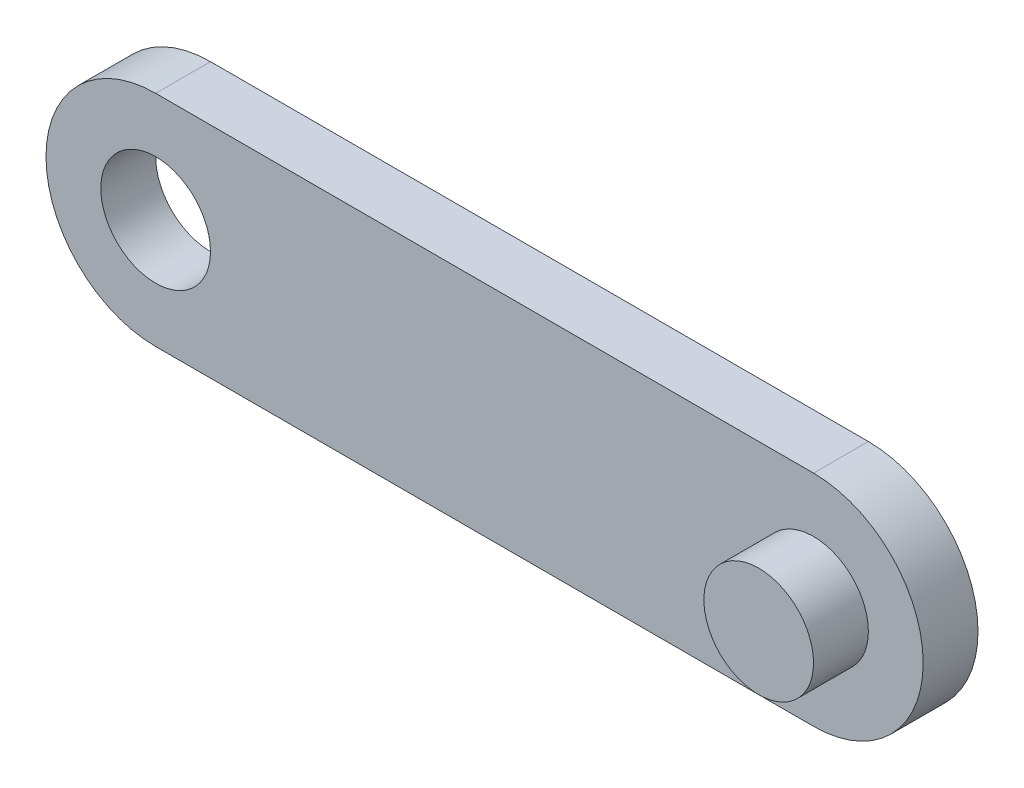
SolidWorks part; units mm, degrees
ref_plane "Front Plane" through (0, 0, 0) normal (0, 0, 1) x (1, 0, 0)
ref_plane "Top Plane" through (0, 0, 0) normal (0, 1, 0) x (1, 0, 0)
ref_plane "Right Plane" through (0, 0, 0) normal (1, 0, 0) x (0, 0, -1)
sketch "Sketch1" plane through (0, 0, 0) normal (0, 0, 1) x (1, 0, 0)
  line L0 (-60, 0) -> (60, 0) construction
  line L1 (-60, 20) -> (60, 20)
  line L2 (-60, -20) -> (60, -20)
  arc A0 (-60, 20) -> (-60, -20) centre (-60, 0) ccw
  arc A1 (60, -20) -> (60, 20) centre (60, 0) ccw
  circle A2 centre (-60, 0) radius 10
  circle A3 centre (60, 0) radius 10
  point P2 (0, 0)
extrude "Boss-Extrude1" add sketch "Sketch1" along normal blind 10
extrude "Boss-Extrude2" add sketch "Sketch1<2>" along normal blind 20 contours A3 region at (60, 0, 0)
sketch "Sketch1<2>" plane through (0, 0, 0) normal (0, 0, 1) x (1, 0, 0) same geometry as "Sketch1"
